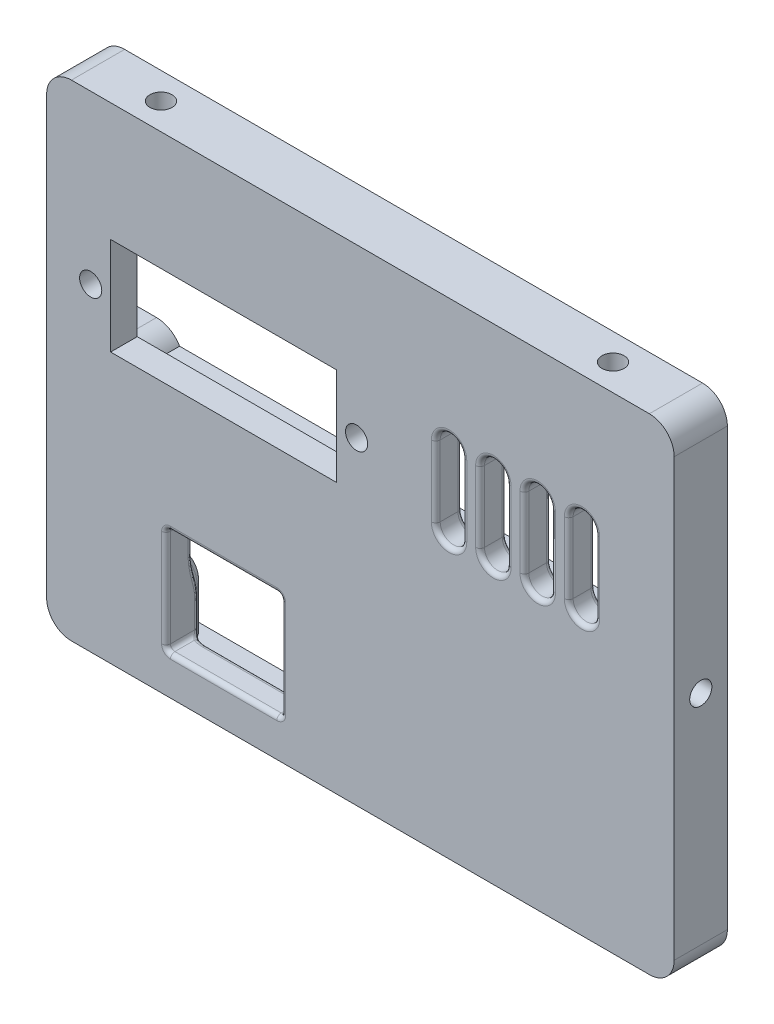
SolidWorks part; units mm, degrees
note: The reader was unsure of these and kept them because the rebuilt part matched: shared geometry of "Эскиз7<2>", "Эскиз9<2>".
ref_plane "Спереди" through (0, 0, 0) normal (0, 0, 1) x (1, 0, 0)
ref_plane "Сверху" through (0, 0, 0) normal (0, 1, 0) x (1, 0, 0)
ref_plane "Справа" through (0, 0, 0) normal (1, 0, 0) x (0, 0, -1)
sketch "Эскиз1" plane through (0, 0, 0) normal (0, 0, 1) x (1, 0, 0)
  line L0 (-32.6, 27.4) -> (32.6, 27.4)
  line L1 (35.4, -24.6) -> (35.4, 24.6)
  line L2 (-32.6, -27.4) -> (32.6, -27.4)
  line L3 (-35.4, 24.6) -> (-35.4, -24.6)
  arc A0 (-32.6, 27.4) -> (-35.4, 24.6) centre (-32.6, 24.6) ccw
  arc A1 (35.4, 24.6) -> (32.6, 27.4) centre (32.6, 24.6) ccw
  arc A2 (32.6, -27.4) -> (35.4, -24.6) centre (32.6, -24.6) ccw
  arc A3 (-35.4, -24.6) -> (-32.6, -27.4) centre (-32.6, -24.6) ccw
  point P11 (0, 27.4)
  point P14 (35.4, 0)
  point P17 (0, -27.4)
  point P20 (-35.4, 0)
  dimension "D3" = 2.8
  dimension "D1" = 70.8
  dimension "D2" = 54.8
extrude "Бобышка-Вытянуть1" add sketch "Эскиз1" along normal blind 3
sketch "Эскиз2" plane through (0, 0, 3) normal (0, 0, 1) x (1, 0, 0)
  line L0 (-32.6, -27.4) -> (32.6, -27.4) construction
  line L1 (-21.93, -23.1) -> (-8.93, -23.1)
  line L2 (-21.93, -23.1) -> (-21.93, -11.1)
  line L3 (-21.93, -11.1) -> (-8.93, -11.1)
  line L4 (-8.93, -23.1) -> (-8.93, -11.1)
  line L5 (-21.93, -23.1) -> (-8.93, -11.1) construction
  line L6 (-21.93, -11.1) -> (-8.93, -23.1) construction
  point P0 (-15.43, -17.1)
  dimension "D1" = 12
  dimension "D2" = 13
  dimension "D3" = 15.43
  dimension "D4" = 10.3
extrude "Вырез-Вытянуть1" cut sketch "Эскиз2" against normal through all
sketch "Эскиз3" plane through (0, 0, 3) normal (0, 0, 1) x (1, 0, 0)
  line L0 (-32.6, -27.4) -> (32.6, -27.4) construction
  line L1 (-28.18, 3.04) -> (-2.68, 3.04)
  line L2 (-28.18, 3.04) -> (-28.18, 14.04)
  line L3 (-28.18, 14.04) -> (-2.68, 14.04)
  line L4 (-2.68, 3.04) -> (-2.68, 14.04)
  line L5 (-28.18, 3.04) -> (-2.68, 14.04) construction
  line L6 (-28.18, 14.04) -> (-2.68, 3.04) construction
  line L7 (-30.43, 8.54) -> (-0.43, 8.54) construction
  line L9 (-32.93, 2.54) -> (2.07, 2.54) construction
  line L10 (-32.93, 2.54) -> (-32.93, 14.54) construction
  line L11 (-32.93, 14.54) -> (2.07, 14.54) construction
  line L12 (2.07, 2.54) -> (2.07, 14.54) construction
  line L13 (-32.93, 2.54) -> (2.07, 14.54) construction
  line L14 (-32.93, 14.54) -> (2.07, 2.54) construction
  line L15 (-8.93, -11.1) -> (-21.93, -11.1) construction
  circle A0 centre (-30.43, 8.54) radius 1.25
  circle A1 centre (-0.43, 8.54) radius 1.25
  point P0 (-15.43, 8.54)
  point P6 (-15.43, -11.1)
  point P8 (-15.43, 8.54)
  dimension "D3" = 2.5
  dimension "D1" = 25.5
  dimension "D2" = 11
  dimension "D4" = 35.94
  dimension "D5" = 30
  dimension "D6" = 35
  dimension "D7" = 12
extrude "Вырез-Вытянуть3" cut sketch "Эскиз3" against normal through all
sketch "Эскиз6" plane through (0, 0, 0) normal (0, 0, -1) x (-1, 0, 0)
  line L0 (-32.6, 27.4) -> (32.6, 27.4)
  line L1 (-35.4, 24.6) -> (-35.4, -24.6)
  line L2 (-32.6, -27.4) -> (32.6, -27.4)
  line L3 (35.4, -24.6) -> (35.4, 24.6)
  line L4 (-32.4, 24.4) -> (-28.5, 24.4)
  line L5 (32.4, -24.4) -> (32.4, -3)
  line L6 (-32.4, -24.4) -> (-28.5, -24.4)
  line L7 (-32.4, 24.4) -> (-32.4, 3)
  line L8 (0, 1.5) -> (0, -1.5) construction
  line L10 (-26.4, -1.5) -> (26.4, -1.5)
  line L11 (0, 32.9332) -> (0, -35.2988) construction
  line L12 (25.5, 21.9) -> (-25.5, 21.9) construction
  line L13 (25.5, -21.9) -> (-25.5, -21.9) construction
  line L14 (-22.5, 24.4) -> (22.5, 24.4)
  line L15 (-22.5, 16.4) -> (-28.5, 16.4)
  line L16 (-22.5, 16.4) -> (-22.5, 27.4)
  line L17 (-22.5, 27.4) -> (-28.5, 27.4)
  line L18 (-28.5, 16.4) -> (-28.5, 27.4)
  line L19 (-22.5, 16.4) -> (-28.5, 27.4) construction
  line L20 (-22.5, 27.4) -> (-28.5, 16.4) construction
  line L21 (22.5, 16.4) -> (28.5, 16.4)
  line L22 (22.5, 16.4) -> (22.5, 27.4)
  line L23 (22.5, 27.4) -> (28.5, 27.4)
  line L24 (28.5, 16.4) -> (28.5, 27.4)
  line L25 (22.5, 16.4) -> (28.5, 27.4) construction
  line L26 (22.5, 27.4) -> (28.5, 16.4) construction
  line L27 (22.5, -27.4) -> (28.5, -27.4)
  line L28 (22.5, -27.4) -> (22.5, -16.4)
  line L29 (22.5, -16.4) -> (28.5, -16.4)
  line L30 (28.5, -27.4) -> (28.5, -16.4)
  line L31 (22.5, -27.4) -> (28.5, -16.4) construction
  line L32 (22.5, -16.4) -> (28.5, -27.4) construction
  line L33 (-28.5, -27.4) -> (-22.5, -27.4)
  line L34 (-28.5, -27.4) -> (-28.5, -16.4)
  line L35 (-28.5, -16.4) -> (-22.5, -16.4)
  line L36 (-22.5, -27.4) -> (-22.5, -16.4)
  line L37 (-28.5, -27.4) -> (-22.5, -16.4) construction
  line L38 (-28.5, -16.4) -> (-22.5, -27.4) construction
  line L39 (-32.4, 24.4) -> (32.4, 24.4) construction
  line L40 (28.5, 24.4) -> (32.4, 24.4)
  line L41 (-32.4, -3) -> (-32.4, -24.4)
  line L42 (-32.4, 24.4) -> (-32.4, -24.4) construction
  line L43 (32.4, 3) -> (32.4, 24.4)
  line L44 (32.4, -24.4) -> (32.4, 24.4) construction
  line L45 (28.5, -24.4) -> (32.4, -24.4)
  line L46 (-32.4, -24.4) -> (32.4, -24.4) construction
  line L47 (-22.5, -24.4) -> (22.5, -24.4)
  line L48 (-2.6445, 0) -> (5.4228, 0) construction
  line L49 (-26.4, 1.5) -> (26.4, 1.5)
  line L50 (26.4, -3) -> (35.4, -3)
  line L51 (26.4, -3) -> (26.4, 3)
  line L52 (26.4, 3) -> (35.4, 3)
  line L53 (35.4, -3) -> (35.4, 3)
  line L54 (26.4, -3) -> (35.4, 3) construction
  line L55 (26.4, 3) -> (35.4, -3) construction
  line L56 (-26.4, -3) -> (-35.4, -3)
  line L57 (-26.4, -3) -> (-26.4, 3)
  line L58 (-26.4, 3) -> (-35.4, 3)
  line L59 (-35.4, -3) -> (-35.4, 3)
  line L60 (-26.4, -3) -> (-35.4, 3) construction
  line L61 (-26.4, 3) -> (-35.4, -3) construction
  arc A0 (-32.6, 27.4) -> (-35.4, 24.6) centre (-32.6, 24.6) ccw
  arc A1 (-35.4, -24.6) -> (-32.6, -27.4) centre (-32.6, -24.6) ccw
  arc A2 (32.6, -27.4) -> (35.4, -24.6) centre (32.6, -24.6) ccw
  arc A3 (35.4, 24.6) -> (32.6, 27.4) centre (32.6, 24.6) ccw
  arc A4 (32.4, 24.4) -> (32.4, 24.4) centre (32.4, 24.4) ccw
  arc A5 (32.4, -24.4) -> (32.4, -24.4) centre (32.4, -24.4) ccw
  arc A6 (-32.4, -24.4) -> (-32.4, -24.4) centre (-32.4, -24.4) ccw
  arc A7 (-32.4, 24.4) -> (-32.4, 24.4) centre (-32.4, 24.4) ccw
  point P38 (0, 0)
  point P48 (0, 21.9)
  point P51 (0, -21.9)
  point P75 (30.9, 0)
  point P81 (-30.9, 0)
  dimension "D3" = 6
  dimension "D4" = 11
  dimension "D5" = 51
  dimension "D6" = 6
  dimension "D7" = 9
  dimension "D2" = 3
extrude "Бобышка-Вытянуть3" add sketch "Эскиз6" along normal blind 3
fillet "Скругление7" radius 3 12 edges at (28.5, -16.4, -1.5) (22.5, -16.4, -1.5) (-22.5, -16.4, -1.5) (-28.5, -16.4, -1.5) (-28.5, 16.4, -1.5) (-22.5, 16.4, -1.5) (28.5, 16.4, -1.5) (22.5, 16.4, -1.5) (-26.4, 3, -1.5) (-26.4, -3, -1.5) (26.4, 3, -1.5) (26.4, -3, -1.5)
fillet "Скругление8" radius 3 16 edges at (-28.5, -21.9, -3) (-27.6213, -17.2787, -3) (-22.5, -21.9, -3) (22.5, -21.9, -3) (23.3787, -17.2787, -3) (28.5, -21.9, -3) (28.5, 21.9, -3) (22.5, 21.9, -3) (23.3787, 17.2787, -3) (-22.5, 21.9, -3) (-28.5, 21.9, -3) (-27.6213, 17.2787, -3) (-23.3787, -17.2787, -3) (27.6213, -17.2787, -3) (27.6213, 17.2787, -3) (-23.3787, 17.2787, -3)
fillet "Скругление9" radius 3 16 edges at (28.5, -21.9, 0) (22.5, -21.9, 0) (23.3787, -17.2787, 0) (-22.5, -21.9, 0) (-28.5, -21.9, 0) (-27.6213, -17.2787, 0) (-28.5, 21.9, 0) (-27.6213, 17.2787, 0) (-22.5, 21.9, 0) (22.5, 21.9, 0) (23.3787, 17.2787, 0) (28.5, 21.9, 0) (27.6213, -17.2787, 0) (-23.3787, -17.2787, 0) (-23.3787, 17.2787, 0) (27.6213, 17.2787, 0)
sketch "Эскиз7" plane through (0, -27.4, 0) normal (0, -1, 0) x (1, 0, 0)
  line L0 (0, 26.5617) -> (0, -19.5255) construction
  line L1 (25.5, 0) -> (-25.5, 0) construction
  circle A0 centre (-25.5, 0) radius 1.25
  circle A1 centre (25.5, 0) radius 1.25
  point P6 (0, 0)
  dimension "D2" = 2.5
  dimension "D1" = 51
extrude "Вырез-Вытянуть6" cut sketch "Эскиз7" against normal blind 9
extrude "Вырез-Вытянуть7" cut sketch "Эскиз7<2>" along normal blind 9 from offset 54.8 offset against normal yes
sketch "Эскиз7<2>" plane through (0, -27.4, 0) normal (0, -1, 0) x (1, 0, 0) same geometry as "Эскиз7"
sketch "Эскиз9" plane through (35.4, 0, 0) normal (1, 0, 0) x (0, 0, -1)
  circle A0 centre (0, 0) radius 1.25
  dimension "D1" = 2.5
extrude "Вырез-Вытянуть9" cut sketch "Эскиз9" against normal blind 7
extrude "Вырез-Вытянуть10" cut sketch "Эскиз9<2>" along normal blind 7 from offset 70.8 offset against normal yes
sketch "Эскиз9<2>" plane through (35.4, 0, 0) normal (1, 0, 0) x (0, 0, -1) same geometry as "Эскиз9"
sketch "Эскиз8" plane through (0, 0, 3) normal (0, 0, 1) x (1, 0, 0)
  line L0 (10, 4.54) -> (10, 12.54) construction
  line L1 (8.5, 4.54) -> (8.5, 12.54)
  line L2 (11.5, 4.54) -> (11.5, 12.54)
  line L3 (-2.68, 14.04) -> (31.095, 14.04) construction
  line L4 (-2.68, 3.04) -> (32.2967, 3.04) construction
  line L6 (15, 4.54) -> (15, 12.54) construction
  line L7 (13.5, 4.54) -> (13.5, 12.54)
  line L8 (16.5, 4.54) -> (16.5, 12.54)
  line L9 (20, 4.54) -> (20, 12.54) construction
  line L10 (18.5, 4.54) -> (18.5, 12.54)
  line L11 (21.5, 4.54) -> (21.5, 12.54)
  line L12 (25, 4.54) -> (25, 12.54) construction
  line L13 (23.5, 4.54) -> (23.5, 12.54)
  line L14 (26.5, 4.54) -> (26.5, 12.54)
  arc A0 (8.5, 4.54) -> (11.5, 4.54) centre (10, 4.54) ccw
  arc A1 (11.5, 12.54) -> (8.5, 12.54) centre (10, 12.54) ccw
  arc A2 (13.5, 4.54) -> (16.5, 4.54) centre (15, 4.54) ccw
  arc A3 (16.5, 12.54) -> (13.5, 12.54) centre (15, 12.54) ccw
  arc A4 (18.5, 4.54) -> (21.5, 4.54) centre (20, 4.54) ccw
  arc A5 (21.5, 12.54) -> (18.5, 12.54) centre (20, 12.54) ccw
  arc A6 (23.5, 4.54) -> (26.5, 4.54) centre (25, 4.54) ccw
  arc A7 (26.5, 12.54) -> (23.5, 12.54) centre (25, 12.54) ccw
  point P2 (10, 8.54)
  point P19 (15, 8.54)
  point P26 (20, 8.54)
  point P33 (25, 8.54)
  dimension "D1" = 3
  dimension "D2" = 10
  dimension "D3" = 4
extrude "Вырез-Вытянуть8" cut sketch "Эскиз8" against normal through all
fillet "Скругление10" radius 0.5 47 edges at (26.5, 8.54, 3) (25, 3.04, 3) (23.5, 8.54, 3) (21.5, 8.54, 3) (20, 3.04, 3) (18.5, 8.54, 3) (16.5, 8.54, 3) (15, 3.04, 3) (13.5, 8.54, 3) (11.5, 8.54, 3) (10, 3.04, 3) (8.5, 8.54, 3) (25, 14.04, 3) (20, 14.04, 3) (15, 14.04, 3) (10, 14.04, 3) (-8.93, -17.1, 0) (-8.93, -17.1, 3) (-15.43, -11.1, 0) (-14.6169, -23.1, 0) (-15.43, -11.1, 3) (-15.43, -23.1, 3) (25, 14.04, 0) (26.5, 8.54, 0) (25, 3.04, 0) (20, 14.04, 0) (21.5, 8.54, 0) (20, 3.04, 0) (15, 14.04, 0) (16.5, 8.54, 0) (15, 3.04, 0) (10, 14.04, 0) (11.5, 8.54, 0) (10, 3.04, 0) (23.5, 8.54, 0) (18.5, 8.54, 0) (13.5, 8.54, 0) (8.5, 8.54, 0) (-21.93, -13.3622, 0) (-21.93, -17.1, 3) (-8.93, -23.1, 1.5) (-21.93, -23.1, 1.2605) (-21.93, -11.1, 1.5) (-8.93, -11.1, 1.5) (-21.1515, -23.1, -0.1222) (-21.93, -21.25, -0.479)
equation "\"Ширина короба\" = 71"
equation "\"Высота короба\"= 55"
equation "\"Зазор\"= 0.2"
equation "\"D1@Эскиз1\" = \"Ширина короба\" - \"Зазор\""
equation "\"D2@Эскиз1\"=\"Высота короба\"-\"Зазор\""
equation "\"D3@Эскиз1\"=5-2-\"Зазор\""
equation "\"D3@Эскиз2\"=(53.34/2)-15.24+4"
equation "\"D4@Эскиз2\"=-0.2+3+2+(11/2)"
equation "\"D4@Эскиз3\"=-0.2+3+2+8.5+2.54+2+10.1+2+(12/2)"
equation "\"D5@Эскиз6\"=\"Ширина короба\"-10*2"
equation "\"D1@Эскиз7\"= \"Ширина короба\" - 10 * 2"
equation "\"D19@Вырез-Вытянуть7\"=\"Высота короба\"-\"Зазор\""
equation "\"D19@Вырез-Вытянуть10\"=\"Ширина короба\"-\"Зазор\""
